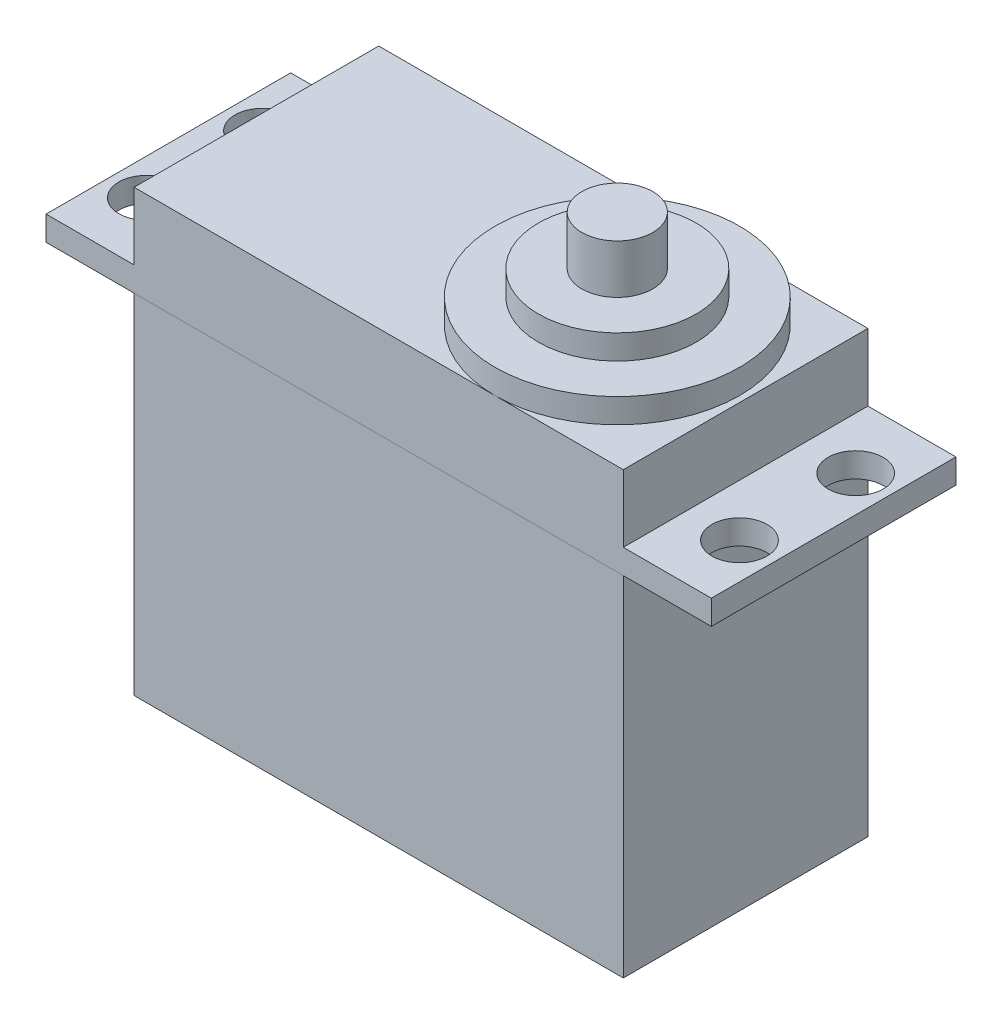
SolidWorks part; units mm, degrees
ref_plane "Alzado" through (0, 0, 0) normal (0, 0, 1) x (1, 0, 0)
ref_plane "Planta" through (0, 0, 0) normal (0, 1, 0) x (1, 0, 0)
ref_plane "Vista lateral" through (0, 0, 0) normal (1, 0, 0) x (0, 0, -1)
sketch "Croquis1" plane through (0, 0, 0) normal (0, 1, 0) x (1, 0, 0)
  line L0 (0, 0) -> (40, 0)
  line L1 (40, 0) -> (40, -20)
  line L2 (0, 0) -> (0, -20)
  line L3 (0, -20) -> (40, -20)
extrude "Saliente-Extruir1" add sketch "Croquis1" along normal blind 28.5
sketch "Croquis2" plane through (0, 28.5, 0) normal (0, 1, 0) x (1, 0, 0)
  line L0 (20, 0) -> (-7.2, 0)
  line L1 (40, 0) -> (0, 0) construction
  line L2 (20, 0) -> (47.2, 0)
  line L3 (-7.2, 0) -> (-7.2, -20.0033)
  line L4 (-7.2, -20.0033) -> (47.2, -20.0033)
  line L5 (47.2, -20.0033) -> (47.2, 0)
extrude "Saliente-Extruir2" add sketch "Croquis2" along normal blind 2
sketch "Croquis3" plane through (0, 30.5, 0) normal (0, 1, 0) x (1, 0, 0)
  line L0 (40, -20) -> (40, 0) construction
  line L1 (0, 0) -> (0, -20) construction
  line L2 (47.2, -10.0017) -> (-7.2, -10.0017) construction
  line L3 (47.2, -20.0033) -> (47.2, 0) construction
  line L4 (-7.2, 0) -> (-7.2, -20.0033) construction
  circle A0 centre (-4.25, -5.2517) radius 2.25
  circle A1 centre (-4.25, -14.7517) radius 2.25
  circle A2 centre (44.25, -5.2517) radius 2.25
  circle A3 centre (44.25, -14.7517) radius 2.25
  dimension "D1" = 4.5
  dimension "D2" = 4.25
  dimension "D3" = 4.25
  dimension "D4" = 4.25
  dimension "D5" = 4.25
  dimension "D6" = 4.75
  dimension "D7" = 4.75
  dimension "D8" = 4.75
  dimension "D9" = 4.75
extrude "Cortar-Extruir1" cut sketch "Croquis3" against normal blind 2.1
sketch "Croquis4" plane through (0, 30.5, 0) normal (0, 1, 0) x (1, 0, 0)
  line L2 (0, 0) -> (0, -20.0033)
  line L3 (-7.2, -20.0033) -> (47.2, -20.0033) construction
  line L4 (0, -20.0033) -> (40.0016, -20.0033)
  line L5 (40.0016, -20.0033) -> (40, 0)
  line L6 (40, 0) -> (0, 0)
extrude "Saliente-Extruir3" add sketch "Croquis4" along normal blind 5.5
sketch "Croquis5" plane through (0, 36, 0) normal (0, 1, 0) x (1, 0, 0)
  line L0 (40.0008, -10.0017) -> (29.5104, -10.0017)
  line L1 (40.0016, -20.0033) -> (40, 0) construction
  circle A0 centre (29.5104, -10.0017) radius 10.0017
extrude "Saliente-Extruir4" add sketch "Croquis5" along normal blind 2 contours A0 region at (19.7916, 36, 10.0017)
sketch "Croquis6" plane through (0, 38, 0) normal (0, 1, 0) x (1, 0, 0)
  circle A0 centre (29.5104, -10.0017) radius 6.45
extrude "Saliente-Extruir5" add sketch "Croquis6" along normal blind 2
sketch "Croquis7" plane through (0, 40, 0) normal (0, 1, 0) x (1, 0, 0)
  circle A0 centre (29.5104, -10.0017) radius 2.9
extrude "Saliente-Extruir6" add sketch "Croquis7" along normal blind 4
